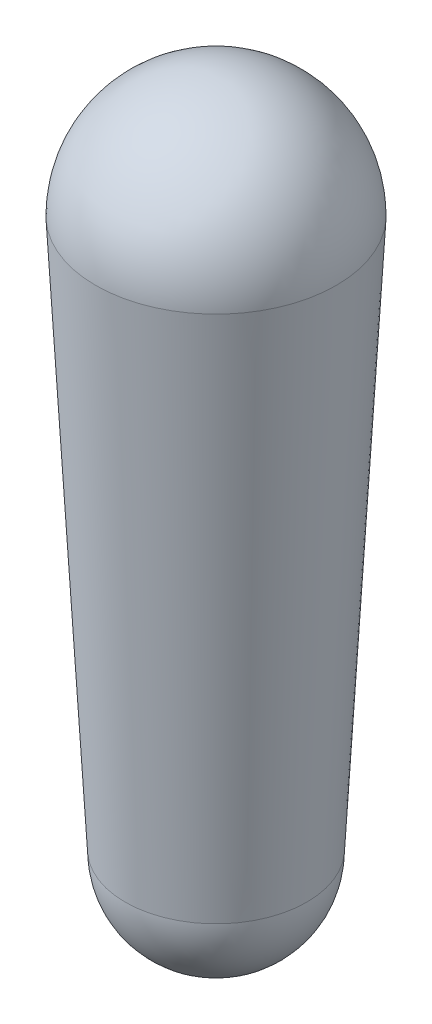
SolidWorks part; units mm, degrees
ref_plane "Front" through (0, 0, 0) normal (0, 0, 1) x (1, 0, 0)
ref_plane "Top" through (0, 0, 0) normal (0, 1, 0) x (1, 0, 0)
ref_plane "Right" through (0, 0, 0) normal (1, 0, 0) x (0, 0, -1)
sketch "Sketch1" plane through (0, 0, 0) normal (0, 1, 0) x (1, 0, 0)
  circle A0 centre (0, 0) radius 90.9577
  dimension "D1" = 181.9155
ref_plane "Plane1" through (0, -415.036, 0) normal (0, 1, 0) x (-1, 0, 0)
sketch "Sketch2" plane through (0, -415.036, 0) normal (0, 1, 0) x (-1, 0, 0)
  circle A0 centre (0, 0) radius 68.7236
  dimension "D1" = 137.4472
ref_axis "Axis1" through (0, -415.036, 0) along (0, 1, 0)
loft "Loft1" add profiles "Sketch1", "Sketch2" connector at (-10.3219, 0, -90.3702) connector at (-10.5801, -415.036, -67.9043)
sketch "Sketch3" plane through (0, -415.036, 0) normal (0, -1, 0) x (1, 0, 0)
  circle A0 centre (0, 0) radius 68.7236 construction
  point P0 (0, 0)
sketch "Sketch4" plane through (0, 0, 0) normal (0, 1, 0) x (-1, 0, 0)
  point P0 (0, 0)
sketch "Sketch5" plane through (0, 0, 0) normal (1, 0, 0) x (0, 0, -1)
  line L0 (0, -483.7596) -> (0, -415.036)
  line L1 (0, -415.036) -> (-68.7236, -415.036)
  line L2 (0, 90.9577) -> (0, 0)
  line L3 (0, 0) -> (-90.9577, 0)
  line L4 (0, 0) -> (0, -415.036) construction
  arc A0 (-68.7236, -415.036) -> (0, -483.7596) centre (0, -415.036) ccw
  arc A1 (-90.9577, 0) -> (0, 90.9577) centre (0, 0) cw
revolve "Revolve1" add sketch "Sketch5" angle 360 about L4
sketch3d "3DSketch1"
  circle A0 centre (0, 0, 0) radius 90.9577 construction
  point P0 (0, 0, -90.9577)
  point P3 (0, 90.9577, 0)
